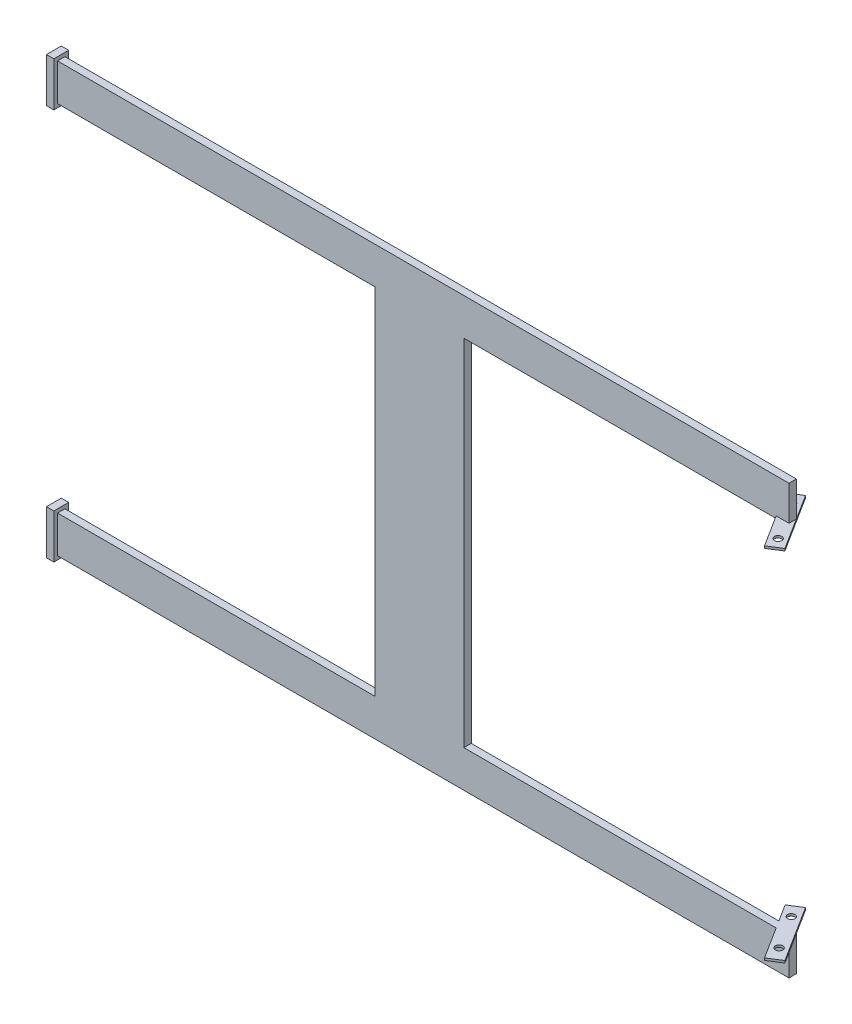
SolidWorks part; units mm, degrees
ref_plane "Front Plane" through (0, 0, 0) normal (0, 0, 1) x (1, 0, 0)
ref_plane "Top Plane" through (0, 0, 0) normal (0, 1, 0) x (1, 0, 0)
ref_plane "Right Plane" through (0, 0, 0) normal (1, 0, 0) x (0, 0, -1)
sketch "Sketch1" plane through (0, 0, 0) normal (0, 0, 1) x (1, 0, 0)
  line L1 (-594.8582, 53.2858) -> (405.1418, 53.2858)
  line L3 (-594.8582, -526.7142) -> (405.1418, -526.7142)
  line L12 (405.1418, 53.2858) -> (405.1418, -526.7142)
  line L13 (-594.8582, -526.7142) -> (-594.8582, 53.2858)
  dimension "D1" = 1000
  dimension "D2" = 580
extrude "Boss-Extrude1" add sketch "Sketch1" along normal blind 10
sketch "Sketch2" plane through (0, 0, 10) normal (0, 0, 1) x (1, 0, 0)
  line L1 (-594.8582, -526.7142) -> (405.1418, -526.7142) construction
  line L6 (-594.8582, 53.2858) -> (-594.8582, -526.7142) construction
  line L16 (405.1418, 3.2858) -> (405.1418, -476.7142)
  line L17 (405.1418, -526.7142) -> (405.1418, 53.2858) construction
  line L18 (405.1418, 3.2858) -> (-34.8582, 3.2858)
  line L19 (-594.8582, 3.2858) -> (-594.8582, -476.7142)
  line L20 (405.1418, 53.2858) -> (-34.8582, 53.2858)
  line L21 (405.1418, 53.2858) -> (-594.8582, 53.2858) construction
  line L22 (-154.8582, 3.2858) -> (-154.8582, -476.7142)
  line L23 (405.1418, 3.2858) -> (-34.8582, 3.2858)
  line L24 (405.1418, 3.2858) -> (405.1418, -476.7142)
  line L25 (405.1418, -476.7142) -> (-34.8582, -476.7142)
  line L26 (-34.8582, 3.2858) -> (-34.8582, -476.7142)
  line L27 (-594.8582, -476.7142) -> (-154.8582, -476.7142)
  line L28 (-594.8582, -476.7142) -> (-594.8582, 3.2858)
  line L29 (-594.8582, 3.2858) -> (-154.8582, 3.2858)
  line L30 (-154.8582, -476.7142) -> (-154.8582, 3.2858)
  line M1 (-594.8582, 53.2858) -> (-594.8582, -526.7142)
  line M3 (405.1418, -526.7142) -> (405.1418, 53.2858)
  dimension "D1" = 50
  dimension "D2" = 50
  dimension "D3" = 440
  dimension "D4" = 440
  dimension "D5" = 50
extrude "Cut-Extrude3" cut sketch "Sketch2" against normal through all contours L18 L26 L25 M3 | L29 L27 L22 M1 region at (185.1418, -236.7142, 10) region at (-374.8582, -236.7142, 10)
shell "Shell2" thickness 1
sketch "Sketch5" plane through (0, -476.7142, 0) normal (0, 1, 0) x (1, 0, 0)
  line L5 (405.1418, 0) -> (431.886, -42.2463)
  line L6 (405.1418, 0) -> (383.7464, 33.797)
  line L7 (383.7464, 33.797) -> (366.8479, 23.0994)
  line L8 (366.8479, 23.0994) -> (414.9874, -52.944)
  line L11 (431.886, -42.2463) -> (414.9874, -52.944)
  dimension "D1" = 50
  dimension "D2" = 40
  dimension "D3" = 90
  dimension "D4" = 20
extrude "Boss-Extrude2" add sketch "Sketch5" against normal blind 3
sketch "Sketch10" plane through (0, 3.2858, 0) normal (0, -1, 0) x (1, 0, 0)
  line L5 (405.1418, 0) -> (431.886, 42.2463)
  line L6 (405.1418, 0) -> (383.7464, -33.797)
  line L7 (383.7464, -33.797) -> (366.8479, -23.0994)
  line L8 (366.8479, -23.0994) -> (414.9875, 52.944)
  line L9 (414.9875, 52.944) -> (431.886, 42.2463)
  dimension "D1" = 40
  dimension "D2" = 50
  dimension "D3" = 20
extrude "Boss-Extrude4" add sketch "Sketch10" against normal blind 3
sketch "Sketch11" plane through (0, 3.2858, 0) normal (0, -1, 0) x (1, 0, 0)
  line L0 (383.7464, -33.797) -> (431.886, 42.2463) construction
  circle A0 centre (415.583, 35.1891) radius 5
  circle A1 centre (384.0776, -14.5783) radius 5
  dimension "D3" = 10
  dimension "D4" = 10
  dimension "D1" = 10
  dimension "D2" = 10
extrude "Cut-Extrude6" cut sketch "Sketch11" against normal through all
sketch "Sketch13" plane through (0, -476.7142, 0) normal (0, 1, 0) x (1, 0, 0)
  line L0 (431.886, -42.2463) -> (383.7464, 33.797) construction
  circle A0 centre (413.1513, -31.3479) radius 5
  circle A1 centre (384.7214, 13.5613) radius 5
  dimension "D1" = 10
  dimension "D3" = 10
  dimension "D4" = 10
  dimension "D2" = 10
extrude "Cut-Extrude7" cut sketch "Sketch13" against normal through all
sketch "Sketch14" plane through (-594.8582, 0, 0) normal (-1, 0, 0) x (0, 0, 1)
  line L8 (-5, -1.7142) -> (15, -1.7142)
  line L9 (15, -1.7142) -> (15, 58.2858)
  line L10 (15, 58.2858) -> (-5, 58.2858)
  line L11 (-5, 58.2858) -> (-5, -1.7142)
  line L12 (-5, -1.7142) -> (15, -1.7142)
  line L13 (15, -1.7142) -> (15, 58.2858)
  line L14 (15, 58.2858) -> (-5, 58.2858)
  line L15 (-5, 58.2858) -> (-5, -1.7142)
  dimension "D1" = 5
extrude "Boss-Extrude5" add sketch "Sketch14" against normal blind 10
sketch "Sketch15" plane through (-594.8582, 0, 0) normal (-1, 0, 0) x (0, 0, 1)
  line L8 (15, -531.7142) -> (15, -471.7142)
  line L9 (15, -471.7142) -> (-5, -471.7142)
  line L10 (-5, -471.7142) -> (-5, -531.7142)
  line L11 (-5, -531.7142) -> (15, -531.7142)
  line L12 (15, -531.7142) -> (15, -471.7142)
  line L13 (15, -471.7142) -> (-5, -471.7142)
  line L14 (-5, -471.7142) -> (-5, -531.7142)
  line L15 (-5, -531.7142) -> (15, -531.7142)
  dimension "D1" = 5
extrude "Boss-Extrude6" add sketch "Sketch15" against normal blind 10
